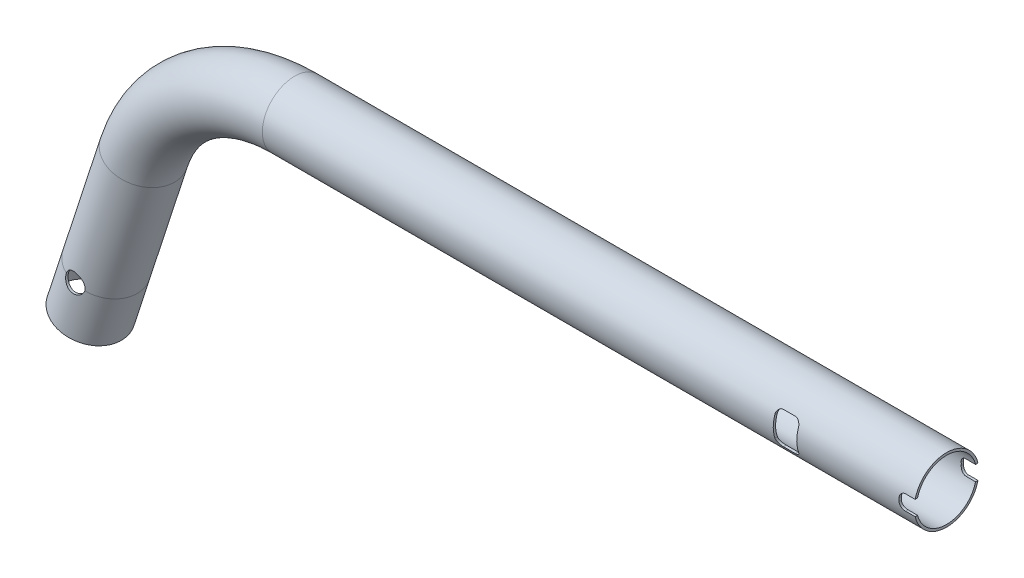
SolidWorks part; units mm, degrees
ref_plane "Front Plane" through (0, 0, 0) normal (0, 0, 1) x (1, 0, 0)
ref_plane "Top Plane" through (0, 0, 0) normal (0, 1, 0) x (1, 0, 0)
ref_plane "Right Plane" through (0, 0, 0) normal (1, 0, 0) x (0, 0, -1)
sketch "Sketch1" plane through (0, 0, 0) normal (0, 0, 1) x (1, 0, 0)
  line L0 (-88.9552, 0) -> (88.9552, 0)
  line L1 (-140.3122, -37.3131) -> (-153.0448, -76.5)
  line L2 (88.9552, 0) -> (132.9552, 0)
  line L3 (-153.0448, -76.5) -> (-158.406, -93)
  arc A0 (-88.9552, 0) -> (-140.3122, -37.3131) centre (-88.9552, -54) ccw
  point P4 (0, 0)
  point P10 (-153.0448, -76.5)
  dimension "D2" = 54
  dimension "D1" = 72
  dimension "D3" = 76.5
  dimension "D4" = 242
  dimension "D5" = 93
  dimension "D6" = 72
  dimension "D7" = 44
ref_plane "Plane1" through (88.9552, 0, 0) normal (1, 0, 0) x (0, 0, -1)
sketch "Sketch3" plane through (88.9552, 0, 0) normal (1, 0, 0) x (0, 0, -1)
  circle A0 centre (0, 0) radius 11
  circle A1 centre (0, 0) radius 10.2
  dimension "D1" = 0.8
  dimension "D2" = 22
sweep "Sweep2" add profiles "Sketch3" path "Sketch1"
ref_axis "Axis1" through (132.9552, 0, 0) along (-1, 0, 0)
ref_axis "Axis2" through (-138.3142, -31.1639, 0) along (-0.309, -0.9511, 0)
sketch "Sketch4" plane through (0, 0, 0) normal (0, 0, 1) x (1, 0, 0)
  line L0 (-163.5064, -73.1008) -> (-142.5832, -79.8992) construction
  line L1 (88.9552, -101.4635) -> (88.9552, 101.4635) construction
  line L2 (132.9552, 0) -> (88.9552, 0) construction
  line L3 (132.9552, -11) -> (132.9552, 11) construction
  line L4 (132.9552, 0) -> (-88.9552, 0) construction
  line L5 (133.7396, 2.5555) -> (133.7396, -2.5555)
  line L6 (86.9552, -5.5) -> (90.9552, -5.5)
  line L7 (84.9552, -3.5) -> (84.9552, 3.5)
  line L8 (86.9552, 5.5) -> (90.9552, 5.5)
  line L9 (92.9552, -3.5) -> (92.9552, 3.5)
  line L10 (84.9552, -5.5) -> (92.9552, 5.5) construction
  line L11 (84.9552, 5.5) -> (92.9552, -5.5) construction
  line L12 (130.5396, -2.5555) -> (133.7396, -2.5555)
  line L13 (128.5396, -0.5555) -> (128.5396, 0.5555)
  line L14 (130.5396, 2.5555) -> (133.7396, 2.5555)
  line L16 (128.5396, -2.5555) -> (132.9552, 0) construction
  line L17 (128.5396, 2.5555) -> (132.9552, 0) construction
  circle A0 centre (-153.0448, -76.5) radius 3.3
  arc A1 (86.9552, -5.5) -> (84.9552, -3.5) centre (86.9552, -3.5) cw
  arc A2 (92.9552, -3.5) -> (90.9552, -5.5) centre (90.9552, -3.5) cw
  arc A3 (90.9552, 5.5) -> (92.9552, 3.5) centre (90.9552, 3.5) cw
  arc A4 (86.9552, 5.5) -> (84.9552, 3.5) centre (86.9552, 3.5) ccw
  arc A5 (130.5396, -2.5555) -> (128.5396, -0.5555) centre (130.5396, -0.5555) cw
  arc A6 (128.5396, 0.5555) -> (130.5396, 2.5555) centre (130.5396, 0.5555) cw
  dimension "D1" = 44
  dimension "D4" = 2
  dimension "D5" = 2
  dimension "D6" = 6.6
  dimension "D2" = 8
  dimension "D3" = 11
extrude "Cut-Extrude1" cut sketch "Sketch4" along normal up to next
sketch "Sketch5" plane through (0, 0, 0) normal (0, 0, 1) x (1, 0, 0)
  line L0 (-162.7456, -73.348) -> (-143.3441, -79.652) construction
  circle A0 centre (-153.0448, -76.5) radius 3.3
extrude "Cut-Extrude2" cut sketch "Sketch5" against normal through all
sketch "Sketch6" plane through (0, 0, 0) normal (0, 0, 1) x (1, 0, 0)
  line L0 (132.9552, 2.5555) -> (129.7552, 2.5555)
  line L1 (127.7552, 0.5555) -> (127.7552, -0.5555)
  line L2 (129.7552, -2.5555) -> (132.9552, -2.5555)
  line L3 (132.9552, -2.5555) -> (132.9552, 2.5555)
  arc A0 (127.7552, -0.5555) -> (129.7552, -2.5555) centre (129.7552, -0.5555) ccw
  arc A1 (127.7552, 0.5555) -> (129.7552, 2.5555) centre (129.7552, 0.5555) cw
  dimension "D1" = 2
  dimension "D2" = 5.2
extrude "Cut-Extrude3" cut sketch "Sketch6" against normal through all and the other way through all
